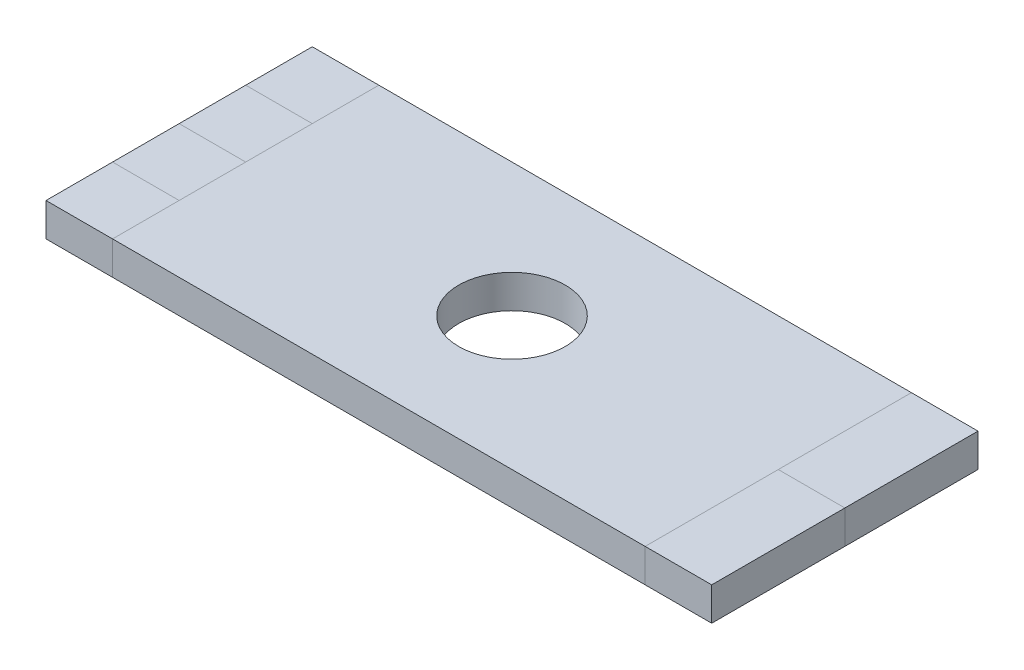
SolidWorks part; units mm, degrees
ref_plane "Front Plane" through (0, 0, 0) normal (0, 0, 1) x (1, 0, 0)
ref_plane "Top Plane" through (0, 0, 0) normal (0, 1, 0) x (1, 0, 0)
ref_plane "Right Plane" through (0, 0, 0) normal (1, 0, 0) x (0, 0, -1)
sketch "Sketch1" plane through (0, 0, 0) normal (0, 1, 0) x (1, 0, 0)
  line L1 (-25.4, -12.7) -> (25.4, -12.7)
  line L2 (-25.4, -12.7) -> (-25.4, 12.7)
  line L3 (-25.4, 12.7) -> (25.4, 12.7)
  line L4 (25.4, -12.7) -> (25.4, 12.7)
  line L5 (-25.4, -12.7) -> (25.4, 12.7) construction
  line L6 (-25.4, 12.7) -> (25.4, -12.7) construction
  circle A0 centre (0, 0) radius 5.08
  point P0 (0, 0)
  dimension "D3" = 10.16
  dimension "D1" = 50.8
  dimension "D2" = 25.4
extrude "Boss-Extrude1" add sketch "Sketch1" along normal blind 3.175
sketch "Sketch2" plane through (-25.4, 0, 0) normal (-1, 0, 0) x (0, 0, 1)
  line L0 (-12.7, 0) -> (12.7, 0) construction
  line L3 (-12.7, 3.175) -> (-6.35, 3.175)
  line L4 (-12.7, 3.175) -> (-12.7, 0)
  line L5 (-12.7, 0) -> (-6.35, 0)
  line L6 (-6.35, 3.175) -> (-6.35, 0)
  line L7 (-12.7, 3.175) -> (12.7, 3.175) construction
  line L8 (-6.35, 0) -> (0, 0)
  line L9 (-6.35, 0) -> (-6.35, 3.175)
  line L10 (-6.35, 3.175) -> (0, 3.175)
  line L11 (0, 0) -> (0, 3.175)
  line L13 (0, 3.175) -> (6.35, 3.175)
  line L14 (0, 3.175) -> (0, 0)
  line L15 (0, 0) -> (6.35, 0)
  line L16 (6.35, 3.175) -> (6.35, 0)
  line L17 (6.35, 3.175) -> (12.7, 3.175)
  line L18 (6.35, 3.175) -> (6.35, 0)
  line L19 (6.35, 0) -> (12.7, 0)
  line L20 (12.7, 3.175) -> (12.7, 0)
  line M11 (-12.7, 0) -> (12.7, 0)
  line M12 (12.7, 0) -> (12.7, 3.175)
  line M13 (12.7, 3.175) -> (-12.7, 3.175)
  line M14 (-12.7, 3.175) -> (-12.7, 0)
  dimension "D1" = 6.35
  dimension "D2" = 6.35
extrude "Boss-Extrude3" add sketch "Sketch2" along normal blind 6.35 separate body contours L6 M13 M14 M11 region at (-25.4, 1.5875, -9.525)
extrude "Boss-Extrude4" add sketch "Sketch2<4>" along normal blind 6.35 separate body contours L11 L6 M11 M13 region at (-25.4, 1.5875, -3.175)
sketch "Sketch2<4>" plane through (-25.4, 0, 0) normal (-1, 0, 0) x (0, 0, 1) same geometry as "Sketch2"
extrude "Boss-Extrude6" add sketch "Sketch2<6>" along normal blind 6.35 separate body contours L16 L11 M13 M11 region at (-25.4, 1.5875, 3.175)
sketch "Sketch2<6>" plane through (-25.4, 0, 0) normal (-1, 0, 0) x (0, 0, 1) same geometry as "Sketch2"
extrude "Boss-Extrude7" add sketch "Sketch2<7>" along normal blind 6.35 separate body contours L16 M13 M11 M12 region at (-25.4, 1.5875, 9.525)
sketch "Sketch2<7>" plane through (-25.4, 0, 0) normal (-1, 0, 0) x (0, 0, 1) same geometry as "Sketch2"
sketch "Sketch4" plane through (25.4, 0, 0) normal (1, 0, 0) x (0, 0, -1)
  line L0 (-12.7, 0) -> (12.7, 0) construction
  line L1 (-12.7, 0) -> (0, 0)
  line L2 (-12.7, 0) -> (-12.7, 3.175)
  line L3 (-12.7, 3.175) -> (0, 3.175)
  line L4 (0, 0) -> (0, 3.175)
  line L5 (-12.7, 3.175) -> (-12.7, 0) construction
  line L6 (-12.7, 3.175) -> (12.7, 3.175) construction
  line L8 (0, 3.175) -> (12.7, 3.175)
  line L9 (0, 3.175) -> (0, 0)
  line L10 (0, 0) -> (12.7, 0)
  line L11 (12.7, 3.175) -> (12.7, 0)
  line M1 (-12.7, 0) -> (12.7, 0)
  line M2 (12.7, 0) -> (12.7, 3.175)
  line M3 (12.7, 3.175) -> (-12.7, 3.175)
  line M4 (-12.7, 3.175) -> (-12.7, 0)
extrude "Boss-Extrude8" add sketch "Sketch4" along normal blind 6.35 separate body contours L4 M1 M3 M4 region at (25.4, 1.5875, 6.35)
extrude "Boss-Extrude9" add sketch "Sketch4<3>" along normal blind 6.35 separate body contours L4 M1 M2 M3 region at (25.4, 1.5875, -6.35)
sketch "Sketch4<3>" plane through (25.4, 0, 0) normal (1, 0, 0) x (0, 0, -1) same geometry as "Sketch4"
